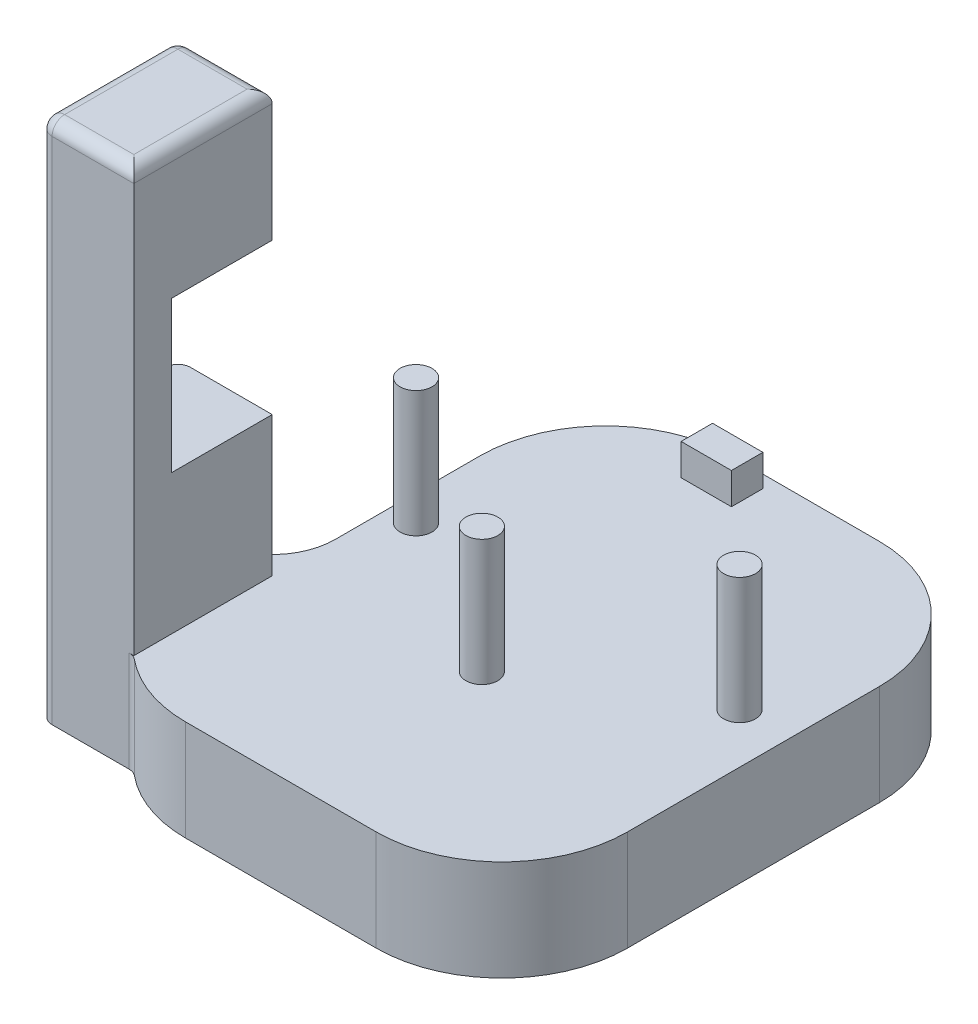
SolidWorks part; units mm, degrees
ref_plane "Front Plane" through (0, 0, 0) normal (0, 0, 1) x (1, 0, 0)
ref_plane "Top Plane" through (0, 0, 0) normal (0, 1, 0) x (1, 0, 0)
ref_plane "Right Plane" through (0, 0, 0) normal (1, 0, 0) x (0, 0, -1)
sketch "Sketch5" plane through (0, 0, 0) normal (0, 1, 0) x (1, 0, 0)
  line L1 (31.75, 40) -> (-31.75, 40)
  line L2 (31.75, 40) -> (31.75, -40)
  line L3 (31.75, -40) -> (-31.75, -40)
  line L4 (-31.75, 40) -> (-31.75, -40)
  line L5 (31.75, 40) -> (-31.75, -40) construction
  line L6 (31.75, -40) -> (-31.75, 40) construction
  point P0 (0, 0)
  dimension "D1" = 80
  dimension "D2" = 63.5
extrude "Boss-Extrude4" add sketch "Sketch5" along normal blind 16
sketch "Sketch6" plane through (0, 16, 0) normal (0, 1, 0) x (1, 0, 0)
  line L0 (31.75, 40) -> (-31.75, 40) construction
  line L1 (-4.75, 38) -> (-12.75, 38)
  line L2 (-4.75, 38) -> (-4.75, 33)
  line L3 (-4.75, 33) -> (-12.75, 33)
  line L4 (-12.75, 38) -> (-12.75, 33)
  line L5 (-4.75, 38) -> (-12.75, 33) construction
  line L6 (-4.75, 33) -> (-12.75, 38) construction
  line L9 (0, 0) -> (0, 40) construction
  line L10 (-31.75, 40) -> (-31.75, -40) construction
  point P0 (-8.75, 35.5)
  dimension "D1" = 8
  dimension "D2" = 5
  dimension "D3" = 2
  dimension "D4" = 19
extrude "Boss-Extrude5" add sketch "Sketch6" along normal blind 5 contours L3 L4 L1 L2
sketch "Sketch9" plane through (0, 0, 0) normal (0, 1, 0) x (1, 0, 0)
  line L0 (-31.75, 40) -> (-31.75, -40) construction
  line L5 (-31.75, -35) -> (-46.75, -35)
  line L6 (-31.75, -35) -> (-31.75, -13)
  line L7 (-31.75, -13) -> (-46.75, -13)
  line L8 (-46.75, -35) -> (-46.75, -13)
  line L9 (-31.75, -40) -> (31.75, -40) construction
  point P13 (-39.25, -13)
  dimension "D4" = 5
  dimension "D5" = 22
  dimension "D6" = 7.5
sketch "Sketch13" plane through (0, 16, 0) normal (0, 1, 0) x (1, 0, 0)
  line L0 (-31.75, 40) -> (-31.75, -40) construction
  line L2 (-31.75, -40) -> (31.75, -40) construction
  circle A0 centre (-27.6098, 5.72) radius 2.54
  circle A1 centre (23.8252, 5.72) radius 2.54
  circle A2 centre (-1.905, -9.52) radius 2.54
  dimension "D1" = 4.1402
  dimension "D3" = 5.08
  dimension "D4" = 51.435
  dimension "D6" = 5.08
  dimension "D7" = 5.08
  dimension "D2" = 45.72
  dimension "D5" = 45.72
  dimension "D8" = 25.7048
  dimension "D9" = 15.24
extrude "Boss-Extrude8" add sketch "Sketch13" along normal blind 20
extrude "Boss-Extrude10" add sketch "Sketch9" along normal blind 83 contours L8 L7 L6 L5
sketch "Sketch14" plane through (0, 0, 13) normal (0, 0, -1) x (-1, 0, 0)
  line L0 (31.75, 83) -> (31.75, 16) construction
  line L1 (31.75, 38.2) -> (46.75, 38.2)
  line L2 (31.75, 38.2) -> (31.75, 62.2)
  line L3 (31.75, 62.2) -> (46.75, 62.2)
  line L4 (46.75, 38.2) -> (46.75, 62.2)
  line L5 (46.75, 83) -> (46.75, 0) construction
  line L6 (31.75, 83) -> (46.75, 83) construction
  dimension "D1" = 20.8
  dimension "D2" = 24
extrude "Cut-Extrude1" cut sketch "Sketch14" against normal blind 16 contours L3 L4 L1 L2
fillet "Fillet1" radius 20 4 edges at (-31.75, 8, -40) (31.75, 8, -40) (-31.75, 8, 40) (31.75, 8, 40)
fillet "Fillet2" radius 10 1 edges at (-31.75, 8, 13)
fillet "Fillet3" radius 2 3 edges at (-31.75, 8, 35) (-46.75, 41.5, 35) (-46.75, 19.1, 13)
fillet "Fillet4" radius 2 1 edges at (-46.75, 72.6, 13)
fillet "Fillet6" radius 2 6 edges at (-31.75, 83, 24) (-38.25, 83, 35) (-46.1642, 83, 34.4142) (-46.75, 83, 24) (-46.1642, 83, 13.5858) (-38.25, 83, 13)
